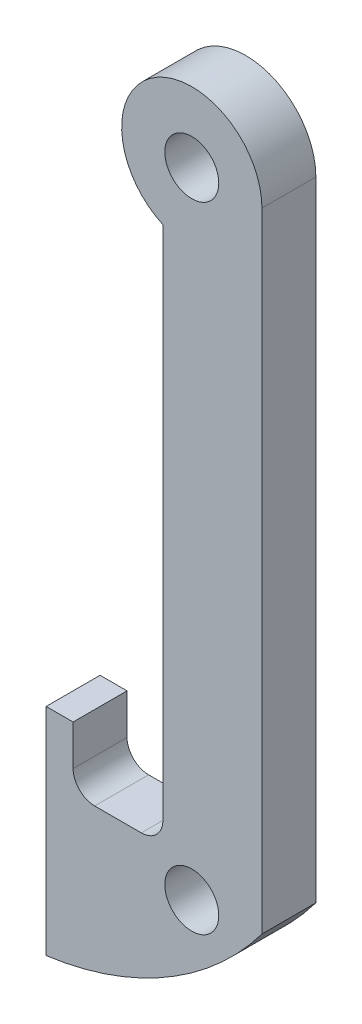
SolidWorks part; units mm, degrees
ref_plane "Front Plane" through (0, 0, 0) normal (0, 0, 1) x (1, 0, 0)
ref_plane "Top Plane" through (0, 0, 0) normal (0, 1, 0) x (1, 0, 0)
ref_plane "Right Plane" through (0, 0, 0) normal (1, 0, 0) x (0, 0, -1)
sketch "Sketch1" plane through (0, 0, 0) normal (0, 0, 1) x (1, 0, 0)
  line L0 (8.255, 0) -> (8.255, -74.0002)
  line L1 (-3.4015, -7.5216) -> (-3.4015, -68.2491)
  line L2 (-5.9415, -70.7891) -> (-11.43, -70.7891)
  line L3 (-13.97, -68.2491) -> (-13.97, -63.5)
  line L4 (-13.97, -63.5) -> (-17.145, -63.5)
  line L5 (-17.145, -63.5) -> (-17.145, -88.9)
  line L6 (0, 0) -> (0, -74.668) construction
  arc A0 (8.255, 0) -> (-3.4015, -7.5216) centre (0, 0) ccw
  circle A1 centre (0, 0) radius 3.175
  arc A2 (-17.145, -88.9) -> (8.255, -74.0002) centre (-22.225, -51.1402) ccw
  arc A3 (-11.43, -70.7891) -> (-13.97, -68.2491) centre (-11.43, -68.2491) cw
  arc A4 (-5.9415, -70.7891) -> (-3.4015, -68.2491) centre (-5.9415, -68.2491) ccw
  circle A5 centre (0, -74.668) radius 3.175
  dimension "D1" = 16.51
  dimension "D2" = 2.54
  dimension "D4" = 6.35
  dimension "D7" = 6.35
  dimension "D3" = 25.4
  dimension "D5" = 88.9
  dimension "D8" = 25.4
  dimension "D11" = 5.08
  dimension "D12" = 3.175
extrude "Boss-Extrude1" add sketch "Sketch1" along normal mid plane 6.35
